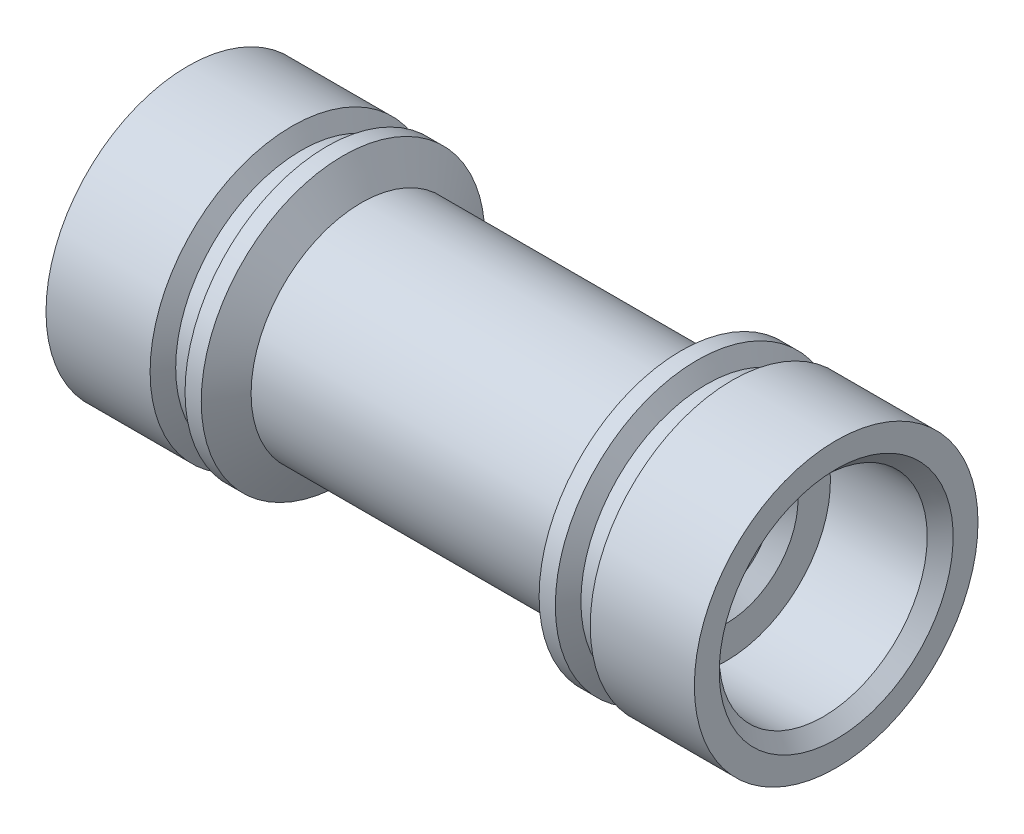
SolidWorks part; units mm, degrees
ref_plane "Front Plane" through (0, 0, 0) normal (0, 0, 1) x (1, 0, 0)
ref_plane "Top Plane" through (0, 0, 0) normal (0, 1, 0) x (1, 0, 0)
ref_plane "Right Plane" through (0, 0, 0) normal (1, 0, 0) x (0, 0, -1)
sketch "Sketch2" plane through (0, 0, 0) normal (0, 0, 1) x (1, 0, 0)
  line L0 (0, 0) -> (0, 28.4375) construction
  line L1 (-12.7, 4.075) -> (-8.4, 4.075) construction
  line L2 (-12.7, 4.075) -> (-12.7, -4.075) construction
  line L3 (-12.7, -4.075) -> (-8.4, -4.075) construction
  line L4 (-8.4, 4.075) -> (-8.4, -4.075) construction
  line L5 (-12.7, 4.075) -> (-8.4, -4.075) construction
  line L6 (-12.7, -4.075) -> (-8.4, 4.075) construction
  line L7 (8.4, 4.5) -> (55.1832, 4.5) construction
  line L8 (8.4, 4.5) -> (8.4, -4.5) construction
  line L9 (8.4, -4.5) -> (55.1832, -4.5) construction
  line L10 (55.1832, 4.5) -> (55.1832, -4.5) construction
  line L11 (8.4, 4.5) -> (55.1832, -4.5) construction
  line L12 (8.4, -4.5) -> (55.1832, 4.5) construction
  line L13 (-12.7, 0) -> (55.1832, 0) construction
  line L14 (-12.7, 5.5562) -> (-8.6216, 5.5562)
  line L21 (-5.9035, 4.318) -> (0, 4.318)
  line L22 (-12.7, 5.5562) -> (-12.7, 4.075)
  line L23 (-12.7, 4.075) -> (-8.4, 4.075)
  line L24 (-8.4, 4.075) -> (-8.4, 0)
  line L25 (-8.4, 0) -> (0, 0)
  line L26 (0, 0) -> (0, 4.318)
  line L27 (-33.5594, -5.5562) -> (-33.5594, 5.5562) construction
  line L28 (-8.6216, 5.5562) -> (-8.255, 4.9212)
  line L29 (-8.255, 4.9212) -> (-7.62, 4.9212)
  line L30 (-12.7, 5.5562) -> (12.7, 5.5562) construction
  line L31 (0, 1.6) -> (-12.5, 1.6)
  line L32 (-12.5, 1.6) -> (-14.1, 0)
  line L33 (-12.5, 1.6) -> (-12.5, -1.6) construction
  line L34 (-12.5, 1.6) -> (12.5, 1.6) construction
  line L35 (-8.4, 1.905) -> (-2.748, 1.905)
  line L36 (-2.748, 1.905) -> (-2.748, 0)
  line L37 (-8.4, 2.805) -> (-7.892, 2.297)
  line L38 (-2.748, 1.905) -> (-15.748, 1.905) construction
  line L39 (-2.748, 1.905) -> (-2.748, -1.905) construction
  line L40 (-2.748, -1.905) -> (-15.748, -1.905) construction
  line L41 (-15.748, 1.905) -> (-15.748, -1.905) construction
  line L42 (-7.892, 2.297) -> (-7.892, 0)
  line L46 (-7.62, 4.9212) -> (-7.2534, 5.5562)
  line L47 (-7.2534, 5.5562) -> (-6.6184, 5.5562)
  line L48 (-6.6184, 5.5562) -> (-5.9035, 4.318)
  line L49 (-7.9375, 4.9212) -> (-7.9375, 6.3987) construction
  line L50 (-7.9375, 6.3987) -> (7.9375, 6.3987) construction
  line L51 (-2.748, 1.905) -> (-0.843, 0)
  point P0 (-10.55, 0)
  point P5 (31.7916, 0)
  point P27 (-33.5594, 0)
  point P29 (-12.5, 0)
  point P33 (0, 6.3987)
  point P36 (0, 1.6)
  point P48 (-2.748, 0)
  point P51 (0, 5.5562)
  dimension "D3" = 4.318
  dimension "D4" = 11.1125
  dimension "D5" = 8.15
  dimension "D13" = 45
  dimension "D14" = 25
  dimension "D15" = 3.2
  dimension "D16" = 3.81
  dimension "D17" = 3.048
  dimension "D18" = 1.27
  dimension "D19" = 0.508
  dimension "D20" = 45
  dimension "D21" = 13
  dimension "D11" = 25.4
  dimension "D6" = 60
  dimension "D7" = 0.635
  dimension "D8" = 60
  dimension "D9" = 15.875
  dimension "D10" = 0.635
  dimension "D12" = 0.635
  dimension "D22" = 4.3
  dimension "D23" = 45
revolve "Revolve1" add sketch "Sketch2" angle 360 about L13 region at (-5.6677, 3.5728, 0) region at (-0.8864, 0.9298, 0)
chamfer "Chamfer1" distance 0.508 angle 45 1 edges at (-12.7, -4.075, 0)
mirror "Mirror1" about plane through (0, 0, 0) normal (1, 0, 0) of bodies 101
equation "\"D22@Sketch2\"=4.3mm"
